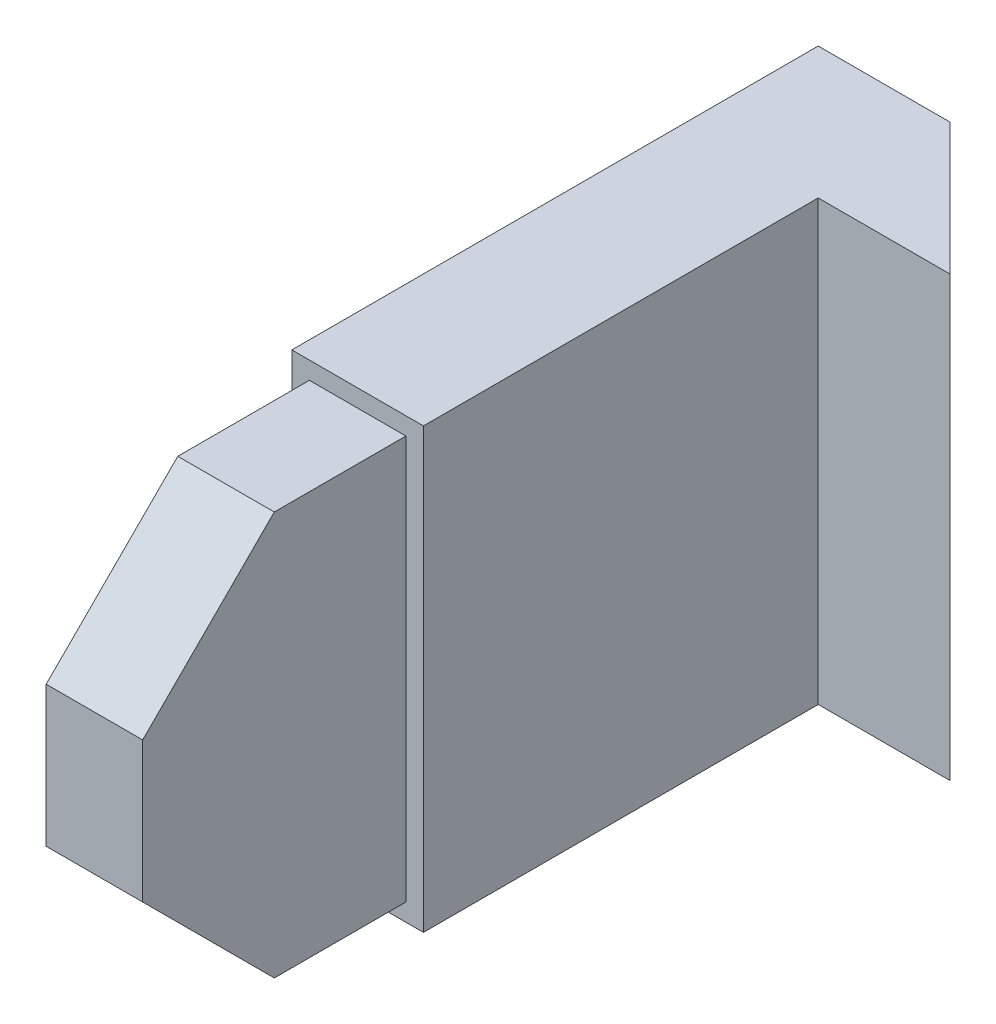
SolidWorks part; units mm, degrees
ref_plane "Front Plane" through (0, 0, 0) normal (0, 0, 1) x (1, 0, 0)
ref_plane "Top Plane" through (0, 0, 0) normal (0, 1, 0) x (1, 0, 0)
ref_plane "Right Plane" through (0, 0, 0) normal (1, 0, 0) x (0, 0, -1)
sketch "Sketch1" plane through (0, 0, 0) normal (0, 1, 0) x (1, 0, 0)
  line L0 (2.25, 1.5) -> (0.75, 3)
  line L1 (-0.75, -3) -> (0.75, -3)
  line L5 (-0.7, -3) -> (0.7, -3)
  line L7 (-0.75, 3) -> (0.75, 3)
  line L8 (-0.75, 3) -> (-0.75, -3)
  line L9 (-0.75, -3) -> (0.75, -3)
  line L10 (0.75, 1.5) -> (0.75, -3)
  line L11 (-0.75, 3) -> (0.75, -3) construction
  line L12 (-0.75, -3) -> (0.75, 3) construction
  line L13 (0.75, 1.5) -> (0.75, 3) construction
  line L15 (0.75, 1.5) -> (2.25, 1.5)
  point P6 (0, 0)
  dimension "D1" = 1.5
  dimension "D3" = 6
extrude "Boss-Extrude1" add sketch "Sketch1" along normal blind 5 contours L1 | L10 L15 L0 L7 L8 L1 region at (0.1389, 0, -0.2222)
sketch "Sketch2" plane through (0, 0, 3) normal (0, 0, 1) x (1, 0, 0)
  line L0 (-0.55, 2.5) -> (0.55, 2.5) construction
  line L1 (0, 4.8) -> (0, 0.2) construction
  line L8 (-0.55, 0.2) -> (0.55, 0.2)
  line L9 (0.55, 0.2) -> (0.55, 4.8)
  line L10 (0.55, 4.8) -> (-0.55, 4.8)
  line L11 (-0.55, 4.8) -> (-0.55, 0.2)
  line L12 (-0.55, 0.2) -> (0.55, 0.2)
  line L13 (0.55, 0.2) -> (0.55, 4.8)
  line L14 (0.55, 4.8) -> (-0.55, 4.8)
  line L15 (-0.55, 4.8) -> (-0.55, 0.2)
  dimension "D1" = 0.2
extrude "Boss-Extrude2" add sketch "Sketch2" along normal blind 3
ref_point "Point1"
ref_axis "Axis1" through (0, 2.5, -6.2512) along (0, 0, 1)
sketch "Sketch3" plane through (0.55, 0, 0) normal (1, 0, 0) x (0, 0, -1)
  line L0 (-6, 0.2) -> (-6, 4.8) construction
  line L1 (-6, 3.3) -> (-4.5, 3.3) construction
  line L2 (-6, 3.3) -> (-6, 4.8) construction
  line L3 (-6, 4.8) -> (-4.5, 4.8) construction
  line L4 (-4.5, 3.3) -> (-4.5, 4.8) construction
  line L5 (-6, 4.8) -> (-3, 4.8) construction
  line L6 (-6, 3.3) -> (-4.5, 4.8)
  line L7 (-6, 3.3) -> (-6, 4.8)
  line L8 (-6, 4.8) -> (-4.5, 4.8)
  arc A0 (-18, 1.4558) -> (-4.5, 9.25) centre (-13.5, 9.25) ccw construction
  arc A1 (-18, 1.4558) -> (-4.5, 9.25) centre (-13.5, 9.25) ccw construction
  dimension "D1" = 1.5
extrude "Cut-Extrude1" cut sketch "Sketch3" against normal up to next
ref_plane "Plane1" through (0, 2.5, 0) normal (0, 1, 0) x (0, 0, 1)
mirror "Mirror1" about plane through (0, 2.5, 0) normal (0, 1, 0) of "Cut-Extrude1"
